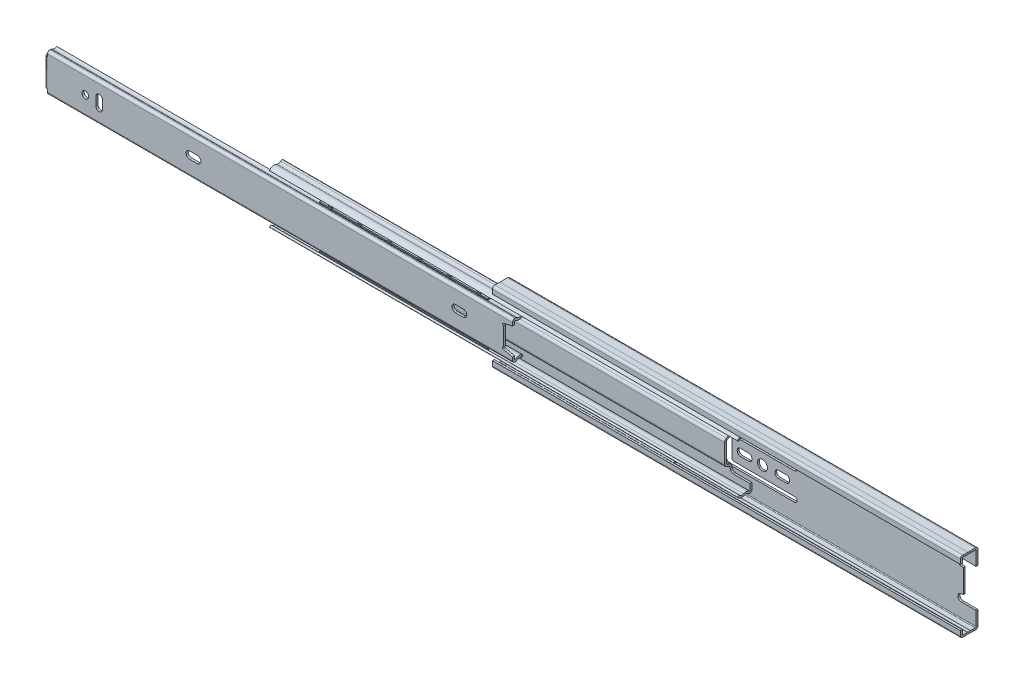
SolidWorks part; units mm, degrees
ref_plane "Front" through (0, 0, 0) normal (0, 0, 1) x (1, 0, 0)
ref_plane "Top" through (0, 0, 0) normal (0, 1, 0) x (1, 0, 0)
ref_plane "Right" through (0, 0, 0) normal (1, 0, 0) x (0, 0, -1)
sketch "Sketch1" plane through (0, 0, 0) normal (1, 0, 0) x (0, 0, -1)
  line L1 (5.6388, 0) -> (-5.6388, 0) construction
  line L4 (-4.1393, 22.8203) -> (-0.7433, 22.6989)
  line L5 (-1.1312, 21.5182) -> (-4.1819, 21.6273)
  line L6 (-4.445, 18.415) -> (-5.6388, 18.415)
  line L7 (-4.445, 21.3734) -> (-4.445, 18.415)
  line L8 (-5.6388, 18.415) -> (-5.6388, 21.3734)
  line L9 (3.9237, 21.6269) -> (0.7619, 21.5441)
  line L10 (5.6388, 0) -> (5.6388, 21.1191)
  line L11 (4.445, 21.1191) -> (4.445, 0)
  line L12 (5.6388, 0) -> (4.445, 0)
  line L13 (-0.7433, 22.6989) -> (3.8925, 22.8203)
  arc A0 (-4.445, 21.3734) -> (-4.1819, 21.6273) centre (-4.191, 21.3734) cw
  arc A1 (-5.6388, 21.3734) -> (-4.1393, 22.8203) centre (-4.191, 21.3734) cw
  arc A3 (3.9237, 21.6269) -> (4.445, 21.1191) centre (3.937, 21.1191) cw
  arc A4 (3.8925, 22.8203) -> (5.6388, 21.1191) centre (3.937, 21.1191) cw
  arc A5 (-1.1312, 21.5182) -> (0.7619, 21.5441) centre (-0.1524, 19.1744) cw
  dimension "D2" = 19.1744
  dimension "D7" = 0.254
  dimension "D8" = 0.508
  dimension "D6" = 2.54
  dimension "D9" = 1.1938
  dimension "D10" = 88.5
  dimension "D1" = 11.2776
  dimension "D3" = 5.7912
  dimension "D4" = 36.83
  dimension "D5" = 1.1938
  dimension "D11" = 87.953
  dimension "D12" = 45.6406
extrude "Extrude1" add sketch "Sketch1" along normal mid plane 299.974
ref_plane "Travel / 2" through (-292.862, 0, 0) normal (-1, 0, 0) x (0, 0, 1)
sketch "Sketch2" plane through (-292.862, 0, 0) normal (-1, 0, 0) x (0, 0, 1)
  line L0 (0.0254, 6.1159) -> (0.0254, 0)
  line L2 (-5.6388, 0) -> (5.6388, 0) construction
  line L3 (5.6388, 21.3734) -> (5.6388, 18.415) construction
  line L7 (-4.445, 21.1191) -> (-4.445, 0) construction
  line L8 (-5.6388, 0) -> (-5.6388, 21.1191) construction
  line L13 (-3.5306, 16.3766) -> (-3.5306, 9.5217)
  line L46 (-2.3867, 7.7262) -> (-0.4146, 6.8065)
  arc A0 (0.0254, 6.1159) -> (-0.4146, 6.8065) centre (-0.7366, 6.1159) ccw
  arc A1 (-1.5056, 17.2916) -> (1.2415, 16.9143) centre (0.1524, 19.1744) ccw
  arc A4 (1.1312, 21.5182) -> (-0.7619, 21.5441) centre (0.1524, 19.1744) ccw construction
  arc A19 (-3.5306, 9.5217) -> (-2.3867, 7.7262) centre (-1.5494, 9.5217) ccw
  arc A25 (-1.5056, 17.2916) -> (-3.5306, 16.3766) centre (-2.3114, 16.3766) ccw
  arc A51 (5.7404, 15.6277) -> (1.2415, 16.9143) centre (2.7686, 13.7451) ccw
  dimension "D2" = 8.4074
  dimension "D3" = 27.4903
  dimension "D6" = 1.9812
  dimension "D8" = 12.2319
  dimension "D10" = 2.5088
  dimension "D11" = 1.2192
  dimension "D4" = 0.762
  dimension "D5" = 4.4704
  dimension "D7" = 115
  dimension "D9" = 19.0435
  dimension "D13" = 11.3792
extrude "Middle Member" add sketch "Sketch2" against normal blind 299.974 separate body thin thin type one direction reverse wall 1.2192
ref_plane "Travel" through (-435.737, 0, 0) normal (-1, 0, 0) x (0, 0, 1)
sketch "Sketch3" plane through (-435.737, 0, 0) normal (-1, 0, 0) x (0, 0, 1)
  line L0 (1.2446, 0) -> (0.0254, 0) construction
  line L1 (-5.6388, 0) -> (-5.6388, 21.1191) construction
  line L56 (7.0612, 0) -> (7.0612, 10.6235)
  line L93 (5.5372, 12.1475) -> (5.1643, 12.1475)
  arc A0 (1.2082, 11.9072) -> (4.2365, 11.8325) centre (2.7686, 13.7451) ccw
  arc A29 (7.0612, 10.6235) -> (5.5372, 12.1475) centre (5.5372, 10.6235) ccw
  arc A53 (5.1643, 12.1475) -> (4.2365, 11.8325) centre (5.1643, 10.6235) ccw
  dimension "D1" = 1.524
  dimension "D4" = 1.524
  dimension "D5" = 2.411
  dimension "D2" = 12.7
  dimension "D3" = 12.1475
  dimension "D6" = 5.853
extrude "Drawer Member" add sketch "Sketch3" against normal blind 299.974 thin thin type one direction wall 1.397
sketch "Sketch6" plane through (0, 0, 7.0612) normal (0, 0, 1) x (1, 0, 0)
  line L1 (-435.737, 0) -> (-433.832, 0)
  line L2 (-435.737, 0) -> (-435.737, 12.1475)
  line L3 (-435.737, 12.1475) -> (-433.832, 12.1475)
  line L4 (-433.832, 0) -> (-433.832, 12.1475)
  line L5 (-135.763, 12.1475) -> (-435.737, 12.1475) construction
  line L7 (-435.737, 10.6235) -> (-435.737, 0) construction
  line L8 (-135.763, 0) -> (-435.737, 0) construction
  dimension "D1" = 1.905
extrude "Cut-Extrude1" cut sketch "Sketch6" against normal through all
sketch "Sketch7" plane through (0, 0, 0) normal (0, -1, 0) x (1, 0, 0)
  line L0 (-433.832, 7.0612) -> (-434.086, 7.0612)
  line L1 (-435.737, 5.4102) -> (-435.737, 0.3041)
  line L2 (-435.737, 0.3041) -> (-434.34, 0.3041)
  line L3 (-434.34, 0.3041) -> (-434.34, 5.4102)
  line L4 (-434.086, 5.6642) -> (-433.832, 5.6642)
  line L5 (-135.763, 5.6642) -> (-433.832, 5.6642) construction
  line L6 (-433.832, 7.0612) -> (-433.832, 5.6642)
  line L7 (-135.763, 0.3041) -> (-433.832, 0.3041) construction
  line L9 (-433.832, 5.087) -> (-433.832, 0.3041) construction
  arc A0 (-434.086, 5.6642) -> (-434.34, 5.4102) centre (-434.086, 5.4102) ccw
  arc A1 (-434.086, 7.0612) -> (-435.737, 5.4102) centre (-434.086, 5.4102) ccw
  dimension "D1" = 0.254
  dimension "D2" = 1.905
extrude "Extrude4" add sketch "Sketch7" against normal blind 8.89
sketch "Sketch8" plane through (0, 0, -4.445) normal (0, 0, 1) x (1, 0, 0)
  line L0 (140.3485, 7.6456) -> (141.7828, 7.493)
  line L1 (149.987, 12.2048) -> (140.5904, 12.2048)
  line L2 (141.7828, 7.493) -> (141.7828, 0)
  line L3 (149.987, 0) -> (-149.987, 0) construction
  line L4 (149.987, 21.1191) -> (149.987, 0) construction
  line L5 (149.987, 12.2048) -> (149.987, 0)
  line L6 (149.987, 0) -> (141.7828, 0)
  arc A0 (140.5904, 12.2048) -> (140.3485, 7.6456) centre (140.5904, 9.9188) ccw
  dimension "D3" = 9.9188
  dimension "D1" = 12.2048
  dimension "D2" = 8.2042
  dimension "D4" = 9.3966
  dimension "D5" = 7.493
extrude "Cut-Extrude2" cut sketch "Sketch8" against normal up to next (1.1938 mm away)
sketch "Sketch11" plane through (0, 0, 7.0612) normal (0, 0, 1) x (1, 0, 0)
  line L0 (-141.478, 5.9678) -> (-141.478, 0)
  line L8 (-135.763, 8.5893) -> (-141.6223, 7.2212)
  line L11 (-141.478, 0) -> (-135.763, 0)
  line L12 (-135.763, 0) -> (-135.763, 8.5893)
  arc A1 (-141.6223, 7.2212) -> (-141.478, 5.9678) centre (-141.4779, 6.6028) ccw
  dimension "D3" = 0.635
  dimension "D1" = 5.715
  dimension "D2" = 8.5893
  dimension "D4" = 5.9678
  dimension "D5" = 103.143
extrude "Cut-Extrude3" cut sketch "Sketch11" against normal up to next (1.397 mm away)
sketch "Sketch12" plane through (0, 0, 1.2446) normal (0, 0, 1) x (1, 0, 0)
  line L0 (7.112, 12.065) -> (-3.048, 12.065)
  line L1 (7.112, 16.3766) -> (7.112, 9.5217) construction
  line L2 (-5.588, 9.525) -> (-5.588, 0)
  line L3 (7.112, 0) -> (-292.862, 0) construction
  line L4 (-5.588, 0) -> (7.112, 0)
  line L5 (7.112, 0) -> (7.112, 12.065)
  arc A0 (-3.048, 12.065) -> (-5.588, 9.525) centre (-3.048, 9.525) ccw
  point P11 (-5.588, 12.065)
  dimension "D3" = 2.54
  dimension "D1" = 12.7
  dimension "D2" = 12.065
extrude "Cut-Extrude4" cut sketch "Sketch12" against normal through all
sketch "Sketch13" plane through (0, 0, -4.445) normal (0, 0, 1) x (1, 0, 0)
  line L0 (-81.5987, 7.112) -> (-106.4272, 7.112)
  line L1 (141.7828, 0) -> (-149.987, 0) construction
  line L2 (-89.6886, 0) -> (-89.6886, 4.2392) construction
  line L3 (-132.5257, 10.287) -> (-81.5987, 10.287)
  line L4 (-149.987, 21.1191) -> (-149.987, 0) construction
  line L5 (-110.2372, 7.112) -> (-132.5257, 7.112)
  line L6 (-109.4752, 0) -> (-109.4752, 6.35)
  line L7 (-107.1892, 6.35) -> (-107.1892, 0)
  line L8 (-87.2121, 2.286) -> (-92.1651, 2.286)
  line L13 (-126.2646, 0) -> (-121.6926, 0)
  line L14 (-118.162, 0) -> (-111.812, 0)
  line L15 (-109.4752, 0) -> (-107.1892, 0)
  line L16 (-104.6746, 0) -> (-100.1026, 0)
  line L17 (-94.4511, 0) -> (-84.9261, 0)
  arc A1 (-132.5257, 10.287) -> (-132.5257, 7.112) centre (-132.5257, 8.6995) ccw
  arc A2 (-109.4752, 6.35) -> (-110.2372, 7.112) centre (-110.2372, 6.35) ccw
  arc A4 (-106.4272, 7.112) -> (-107.1892, 6.35) centre (-106.4272, 6.35) ccw
  arc A7 (-81.5987, 7.112) -> (-81.5987, 10.287) centre (-81.5987, 8.6995) ccw
  arc A8 (-111.812, 0) -> (-118.162, 0) centre (-114.987, 0) ccw
  arc A9 (-121.6926, 0) -> (-126.2646, 0) centre (-123.9786, 0) ccw
  arc A10 (-100.1026, 0) -> (-104.6746, 0) centre (-102.3886, 0) ccw
  arc A11 (-84.9261, 0) -> (-87.2121, 2.286) centre (-87.2121, 0) ccw
  arc A12 (-92.1651, 2.286) -> (-94.4511, 0) centre (-92.1651, 0) ccw
  dimension "D3" = 2.286
  dimension "D4" = 3.175
  dimension "D7" = 8.9916
  dimension "D8" = 21.59
  dimension "D9" = 34.29
  dimension "D10" = 0.762
  dimension "D11" = 17.5387
  dimension "D12" = 9.525
  dimension "D13" = 5.5118
  dimension "D14" = 35
  dimension "D1" = 3.175
  dimension "D2" = 50.927
  dimension "D5" = 2.286
  dimension "D6" = 10.287
extrude "Cut-Extrude5" cut sketch "Sketch13" against normal up to next (1.1938 mm away)
sketch "Sketch32" plane through (0, 0, -5.6388) normal (0, 0, -1) x (-1, 0, 0)
  line L0 (-30.4755, 0) -> (-20.9505, 0)
  line L1 (-16.188, 0) -> (-9.838, 0)
  line L2 (-6.3455, 0) -> (3.1795, 0)
  line L3 (6.545, 0) -> (11.117, 0)
  line L4 (-141.7828, 0) -> (84.9261, 0) construction
  line L5 (132.5257, 10.287) -> (81.5987, 10.287) construction
  line L6 (81.5987, 7.112) -> (106.4272, 7.112) construction
  line L7 (-1.583, 2.286) -> (-1.583, -3.4269) construction
  line L8 (-25.713, 2.286) -> (-25.713, -3.4269) construction
  line L14 (-33.6505, 10.287) -> (9.593, 10.287)
  line L15 (5.021, 7.112) -> (-33.6505, 7.112)
  line L17 (11.117, 8.763) -> (11.117, 0)
  line L18 (6.545, 0) -> (6.545, 5.588)
  line L23 (-28.1895, 2.286) -> (-23.2365, 2.286)
  line L25 (-4.0595, 2.286) -> (0.8935, 2.286)
  arc A0 (118.162, 0) -> (111.812, 0) centre (114.987, 0) ccw construction
  arc A13 (11.117, 8.763) -> (9.593, 10.287) centre (9.593, 8.763) ccw
  arc A14 (6.545, 5.588) -> (5.021, 7.112) centre (5.021, 5.588) ccw
  arc A17 (-33.6505, 10.287) -> (-33.6505, 7.112) centre (-33.6505, 8.6995) ccw
  arc A20 (-20.9505, 0) -> (-23.2365, 2.286) centre (-23.2365, 0) ccw
  arc A21 (-28.1895, 2.286) -> (-30.4755, 0) centre (-28.1895, 0) ccw
  arc A22 (-9.838, 0) -> (-16.188, 0) centre (-13.013, 0) ccw
  arc A24 (3.1795, 0) -> (0.8935, 2.286) centre (0.8935, 0) ccw
  arc A25 (-4.0595, 2.286) -> (-6.3455, 0) centre (-4.0595, 0) ccw
  dimension "D2" = 1.524
  dimension "D3" = 3.175
  dimension "D4" = 9.525
  dimension "D5" = 2.286
  dimension "D6" = 11.43
  dimension "D7" = 12.7
  dimension "D8" = 24.13
  dimension "D9" = 20.6375
  dimension "D10" = 128
  dimension "D1" = 4.572
extrude "Cut-Extrude14" cut sketch "Sketch32" against normal up to next (1.1938 mm away)
sketch "Sketch33" plane through (83.6094, 0.8125, -5.6388) normal (0, 0, -1) x (-1, 0, 0)
  line L0 (-42.8661, -0.8125) -> (-33.3411, -0.8125)
  line L1 (-28.5786, -0.8125) -> (-22.2286, -0.8125)
  line L2 (-18.7361, -0.8125) -> (-9.2111, -0.8125)
  line L3 (-5.8456, -0.8125) -> (-1.2736, -0.8125)
  line L7 (-13.9736, 1.4735) -> (-13.9736, -4.2394) construction
  line L8 (-38.1036, 1.4735) -> (-38.1036, -3.4269) construction
  line L9 (-58.1734, -0.8125) -> (53.1339, -0.8125) construction
  line L10 (93.2024, 9.4745) -> (49.9589, 9.4745) construction
  line L11 (49.9589, 6.2995) -> (88.6304, 6.2995) construction
  line L14 (-46.0411, 9.4745) -> (-2.7976, 9.4745)
  line L15 (-7.3696, 6.2995) -> (-46.0411, 6.2995)
  line L17 (-1.2736, 7.9505) -> (-1.2736, -0.8125)
  line L18 (-5.8456, -0.8125) -> (-5.8456, 4.7755)
  line L23 (-40.5801, 1.4735) -> (-35.6271, 1.4735)
  line L25 (-16.4501, 1.4735) -> (-11.4971, 1.4735)
  arc A1 (201.7714, -0.8125) -> (195.4214, -0.8125) centre (198.5964, -0.8125) ccw construction
  arc A13 (-1.2736, 7.9505) -> (-2.7976, 9.4745) centre (-2.7976, 7.9505) ccw
  arc A14 (-5.8456, 4.7755) -> (-7.3696, 6.2995) centre (-7.3696, 4.7755) ccw
  arc A17 (-46.0411, 9.4745) -> (-46.0411, 6.2995) centre (-46.0411, 7.887) ccw
  arc A20 (-33.3411, -0.8125) -> (-35.6271, 1.4735) centre (-35.6271, -0.8125) ccw
  arc A21 (-40.5801, 1.4735) -> (-42.8661, -0.8125) centre (-40.5801, -0.8125) ccw
  arc A22 (-22.2286, -0.8125) -> (-28.5786, -0.8125) centre (-25.4036, -0.8125) ccw
  arc A24 (-9.2111, -0.8125) -> (-11.4971, 1.4735) centre (-11.4971, -0.8125) ccw
  arc A25 (-16.4501, 1.4735) -> (-18.7361, -0.8125) centre (-16.4501, -0.8125) ccw
  dimension "D2" = 1.524
  dimension "D3" = 3.175
  dimension "D4" = 9.525
  dimension "D5" = 2.286
  dimension "D6" = 11.43
  dimension "D7" = 12.7
  dimension "D8" = 24.13
  dimension "D9" = 20.6375
  dimension "D10" = 224
  dimension "D1" = 4.572
extrude "Cut-Extrude6" cut sketch "Sketch33" against normal up to next (1.1938 mm away)
sketch "Sketch24" plane through (0, 0, 7.0612) normal (0, 0, 1) x (1, 0, 0)
  line L0 (-141.478, 0) -> (-434.086, 0) construction
  line L1 (-400.685, 4.826) -> (-400.685, 0) construction
  line L2 (-402.8694, 2.6416) -> (-402.8694, 0)
  line L3 (-402.8694, 0) -> (-398.5006, 0)
  line L4 (-398.5006, 0) -> (-398.5006, 2.6416)
  line L5 (-344.9955, 0) -> (-335.4705, 0)
  line L6 (-342.7095, 2.286) -> (-337.7565, 2.286)
  line L11 (-435.737, 8.89) -> (-435.737, 0) construction
  line L12 (-340.233, 2.286) -> (-340.233, 0) construction
  circle A0 centre (-409.575, 0) radius 2.1844
  arc A1 (-402.8694, 2.6416) -> (-398.5006, 2.6416) centre (-400.685, 2.6416) cw
  arc A2 (-344.9955, 0) -> (-342.7095, 2.286) centre (-342.7095, 0) cw
  arc A3 (-337.7565, 2.286) -> (-335.4705, 0) centre (-337.7565, 0) cw
  dimension "D1" = 4.3688
  dimension "D4" = 8.89
  dimension "D5" = 2.286
  dimension "D7" = 60.452
  dimension "D2" = 35.052
  dimension "D3" = 4.826
  dimension "D6" = 9.525
extrude "Cut-Extrude13" cut sketch "Sketch24" against normal up to next (1.397 mm away)
sketch "Sketch25" plane through (0, 0, 7.0612) normal (0, 0, 1) x (1, 0, 0)
  line L1 (-141.478, 0) -> (-335.4705, 0) construction
  line L5 (-165.0365, 0) -> (-174.5615, 0)
  line L6 (-337.7565, 2.286) -> (-342.7095, 2.286) construction
  line L7 (-172.2755, 2.286) -> (-167.3225, 2.286)
  line L8 (-169.799, 0) -> (-169.799, 2.286) construction
  arc A1 (-398.5006, 2.6416) -> (-402.8694, 2.6416) centre (-400.685, 2.6416) ccw construction
  arc A3 (-172.2755, 2.286) -> (-174.5615, 0) centre (-172.2755, 0) ccw
  arc A4 (-167.3225, 2.286) -> (-165.0365, 0) centre (-167.3225, 0) cw
  arc A5 (-335.4705, 0) -> (-337.7565, 2.286) centre (-337.7565, 0) ccw construction
  dimension "D1" = 230.886
extrude "Cut D" cut sketch "Sketch25" against normal up to next (1.397 mm away)
ref_plane "Plane3" through (-137.287, 0, 0) normal (-1, 0, 0) x (0, 0, 1)
sketch "Sketch27" plane through (-137.287, 0, 0) normal (-1, 0, 0) x (0, 0, 1)
  line L0 (0.1524, 21.6832) -> (0.1524, 16.6656)
  line L1 (0.1524, 23.635) -> (0.1524, 15.2838) construction
  arc A0 (0.1524, 16.6656) -> (0.1524, 21.6832) centre (0.1524, 19.1744) ccw
  arc A1 (-1.5056, 17.2916) -> (1.2415, 16.9143) centre (0.1524, 19.1744) ccw construction
revolve "Revolve1" add sketch "Sketch27" angle 360 about L1
pattern_linear "LPattern1" count 6 spacing 19.05 along (1, 0, 0) of bodies 128
sketch "Sketch28" plane through (-137.287, 0, 0) normal (-1, 0, 0) x (0, 0, 1)
  line L0 (2.6612, 19.1744) -> (-2.3564, 19.1744) construction
  line L1 (3.9624, 18.7934) -> (-3.6576, 18.7934)
  line L2 (3.9624, 18.7934) -> (3.9624, 19.5554)
  line L3 (3.9624, 19.5554) -> (-3.6576, 19.5554)
  line L4 (-3.6576, 18.7934) -> (-3.6576, 19.5554)
  line L5 (0.1524, 20.5465) -> (0.1524, 17.804) construction
  circle A1 centre (0.1524, 19.1744) radius 2.5088 construction
  point P8 (0.1524, 19.1744)
  dimension "D1" = 7.62
  dimension "D2" = 0.762
extrude "Extrude7" add sketch "Sketch28" along normal blind 6.35 and the other way blind 101.6
ref_plane "Plane4" through (-254.762, 0, 0) normal (-1, 0, 0) x (0, 0, 1)
sketch "Sketch29" plane through (-254.762, 0, 0) normal (-1, 0, 0) x (0, 0, 1)
  line L0 (2.7686, 16.0438) -> (2.7686, 11.4464)
  line L1 (2.7686, 16.6801) -> (2.7686, 10.2973) construction
  arc A0 (2.7686, 11.4464) -> (2.7686, 16.0438) centre (2.7686, 13.7451) ccw
  arc A1 (4.7105, 14.9753) -> (1.7707, 15.816) centre (2.7686, 13.7451) ccw construction
revolve "Revolve2" add sketch "Sketch29" angle 360 about L1
pattern_linear "LPattern2" count 6 spacing 19.05 along (1, 0, 0) of bodies 135
sketch "Sketch30" plane through (-254.762, 0, 0) normal (-1, 0, 0) x (0, 0, 1)
  line L0 (0.4699, 13.7451) -> (5.0673, 13.7451) construction
  line L1 (3.9624, 18.7934) -> (3.9624, 19.5554) construction
  line L2 (0.2286, 14.1261) -> (5.3086, 14.1261)
  line L3 (0.2286, 14.1261) -> (0.2286, 13.3641)
  line L4 (0.2286, 13.3641) -> (5.3086, 13.3641)
  line L5 (5.3086, 14.1261) -> (5.3086, 13.3641)
  line L7 (2.7686, 14.2437) -> (2.7686, 12.7853) construction
  circle A0 centre (2.7686, 13.7451) radius 2.2987 construction
  point P4 (2.7686, 13.7451)
  dimension "D1" = 5.08
extrude "Extrude8" add sketch "Sketch30" along normal blind 6.35 and the other way blind 101.6
mirror "Mirror3" about plane through (0, 0, 0) normal (0, 1, 0) of bodies 126 119 160 117 124 127 159
mirror "Mirror5" about plane through (0, 0, 0) normal (0, 1, 0) of bodies 141 134
sketch "Sketch34" plane through (0, 0, -4.445) normal (0, 0, 1) x (1, 0, 0)
  line L0 (129.6505, 10.287) -> (86.407, 10.287) construction
  line L1 (84.883, 10.287) -> (131.238, 10.287)
  line L2 (84.883, 10.287) -> (84.883, -10.287)
  line L3 (84.883, -10.287) -> (131.238, -10.287)
  line L4 (131.238, 10.287) -> (131.238, -10.287)
  line L5 (84.883, 8.763) -> (84.883, -8.763) construction
  arc A0 (129.6505, -10.287) -> (129.6505, -7.112) centre (129.6505, -8.6995) ccw construction
extrude "Boss-Extrude1" add sketch "Sketch34" against normal up to surface (1.1938 mm away) up to face at (109.013, 3.175, -5.6388)
